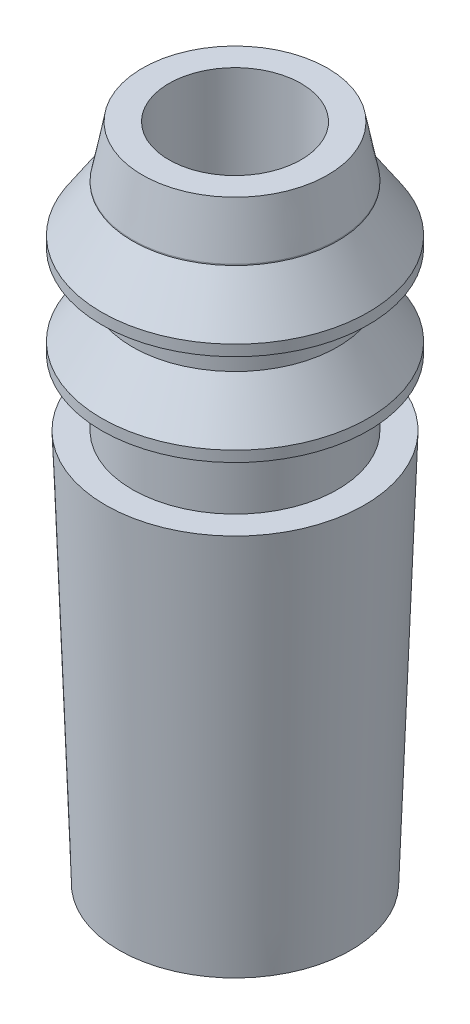
SolidWorks part; units mm, degrees
ref_plane "Front Plane" through (0, 0, 0) normal (0, 0, 1) x (1, 0, 0)
ref_plane "Top Plane" through (0, 0, 0) normal (0, 1, 0) x (1, 0, 0)
ref_plane "Right Plane" through (0, 0, 0) normal (1, 0, 0) x (0, 0, -1)
sketch "Sketch1" plane through (0, 0, 0) normal (0, 1, 0) x (1, 0, 0)
  circle A0 centre (0, 0) radius 1.2
  circle A1 centre (0, 0) radius 0.6
extrude "Boss-Extrude1" add sketch "Sketch1" along normal blind 3.56
chamfer "Chamfer1" distance 0.15 angle 88 1 edges at (0, 0, 1.2) first distance on face at (0, 0, 1.2)
sketch "Sketch2" plane through (0, 0, 0) normal (0, 0, 1) x (1, 0, 0)
  line L0 (-0.9302, 3.56) -> (-0.6, 3.56)
  line L2 (-0.9302, 5.5128) -> (-1.2099, 5.0928)
  line L4 (-0.9302, 4.68) -> (-1.2099, 4.26)
  line L5 (-0.6, 5.986) -> (-0.9302, 5.986)
  line L6 (-0.6, 5.986) -> (-0.6, 3.56)
  line L7 (-0.9302, 4.1628) -> (-0.9302, 3.56)
  line L8 (-0.9302, 4.9942) -> (-0.9302, 4.68)
  line L9 (-0.9302, 5.5128) -> (-0.9302, 5.986)
  line L10 (-1.2099, 5.0928) -> (-1.2099, 4.9942)
  line L11 (1.1743, 3.56) -> (-1.1743, 3.56) construction
  line L12 (0, 3.56) -> (0, 5.718) construction
  line L13 (-1.2099, 4.9942) -> (-0.9302, 4.9942)
  line L14 (-1.2099, 4.26) -> (-1.2099, 4.1628)
  line L15 (-1.2099, 4.1628) -> (-0.9302, 4.1628)
revolve "Revolve1" add sketch "Sketch2" angle 360 about L12
chamfer "Chamfer2" distance 0.09 angle 79 1 edges at (0, 5.986, -0.9302) first distance on face at (0, 5.986, -0.9302)
